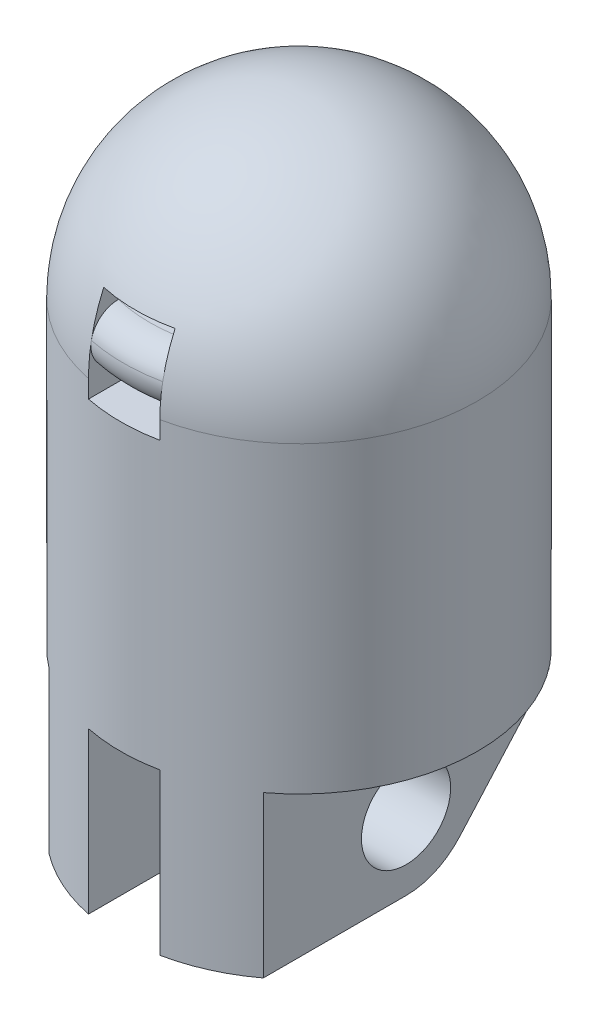
SolidWorks part; units mm, degrees
ref_plane "Front Plane" through (0, 0, 0) normal (0, 0, 1) x (1, 0, 0)
ref_plane "Top Plane" through (0, 0, 0) normal (0, 1, 0) x (1, 0, 0)
ref_plane "Right Plane" through (0, 0, 0) normal (1, 0, 0) x (0, 0, -1)
sketch "Sketch1" plane through (0, 0, 0) normal (0, 0, 1) x (1, 0, 0)
  line L0 (0, 0) -> (0, 5.6026)
  line L1 (0, 0) -> (-12.7, 0)
  line L2 (-12.7, 0) -> (-12.7, 33.02)
  line L6 (0, 5.6026) -> (-2.54, 5.6026)
  line L9 (-2.54, 5.6026) -> (-2.54, 38.1)
  line L10 (-2.54, 38.1) -> (0, 38.1)
  line L11 (0, 38.1) -> (0, 45.72)
  arc A0 (0, 45.72) -> (-12.7, 33.02) centre (0, 33.02) ccw
  dimension "D3" = 25.4
  dimension "D1" = 45.72
  dimension "D2" = 12.7
  dimension "D4" = 2.54
  dimension "D5" = 5.08
revolve "Revolve1" add sketch "Sketch1" angle 360 about L0
sketch "Sketch2" plane through (0, 0, 0) normal (0, -1, 0) x (1, 0, 0)
  line L0 (-2.54, 12.4434) -> (-2.54, -12.4434)
  line L1 (-7.62, 10.16) -> (-7.62, -10.16)
  line L2 (2.54, 12.4434) -> (2.54, -12.4434)
  line L3 (7.62, 10.16) -> (7.62, -10.16)
  circle A0 centre (0, 0) radius 12.7 construction
  arc A1 (-7.62, 10.16) -> (-7.62, -10.16) centre (0, 0) ccw
  arc A2 (-2.54, -12.4434) -> (2.54, -12.4434) centre (0, 0) ccw
  arc A3 (7.62, -10.16) -> (7.62, 10.16) centre (0, 0) ccw
  arc A4 (2.54, 12.4434) -> (-2.54, 12.4434) centre (0, 0) ccw
  dimension "D1" = 2.54
  dimension "D2" = 5.08
  dimension "D3" = 2.54
  dimension "D4" = 5.08
extrude "Cut-Extrude1" cut sketch "Sketch2" against normal blind 11.43
sketch "Sketch3" plane through (-7.62, 0, 0) normal (-1, 0, 0) x (0, 0, 1)
  line L0 (0, -55) -> (0, 55) construction
  line L1 (-10.16, 0) -> (10.16, 0) construction
  line L2 (0, 0) -> (-12.4434, 0)
  line L3 (-12.4434, 0) -> (-12.4434, 11.43)
  line L4 (-3.7964, 1.7046) -> (-12.4434, 11.43)
  circle A0 centre (0, 5.08) radius 3.175
  arc A1 (0, 0) -> (-3.7964, 1.7046) centre (0, 5.08) cw
  dimension "D2" = 6.35
  dimension "D1" = 5.08
extrude "Cut-Extrude2" cut sketch "Sketch3" against normal through all
sketch "Sketch4" plane through (0, 0, 0) normal (0, 0, 1) x (1, 0, 0)
  line L0 (12.7, 33.02) -> (-12.7, 33.02) construction
  line L1 (2.54, 33.02) -> (-2.54, 33.02)
  line L2 (2.54, 33.02) -> (2.54, 31.75)
  line L3 (2.54, 31.75) -> (-2.54, 31.75)
  line L4 (-2.54, 33.02) -> (-2.54, 31.75)
  line L6 (2.54, 36.83) -> (-2.54, 36.83)
  line L7 (2.54, 36.83) -> (2.54, 38.1)
  line L8 (2.54, 38.1) -> (-2.54, 38.1)
  line L9 (-2.54, 36.83) -> (-2.54, 38.1)
  dimension "D1" = 1.27
  dimension "D2" = 1.27
  dimension "D3" = 3.81
extrude "Cut-Extrude3" cut sketch "Sketch4" against normal through all both and the other way through all
fillet "Fillet1" radius 1.905 4 edges at (0, 33.02, -12.7) (0, 36.83, -12.115) (0, 33.02, 12.7) (0, 36.83, 12.115)
